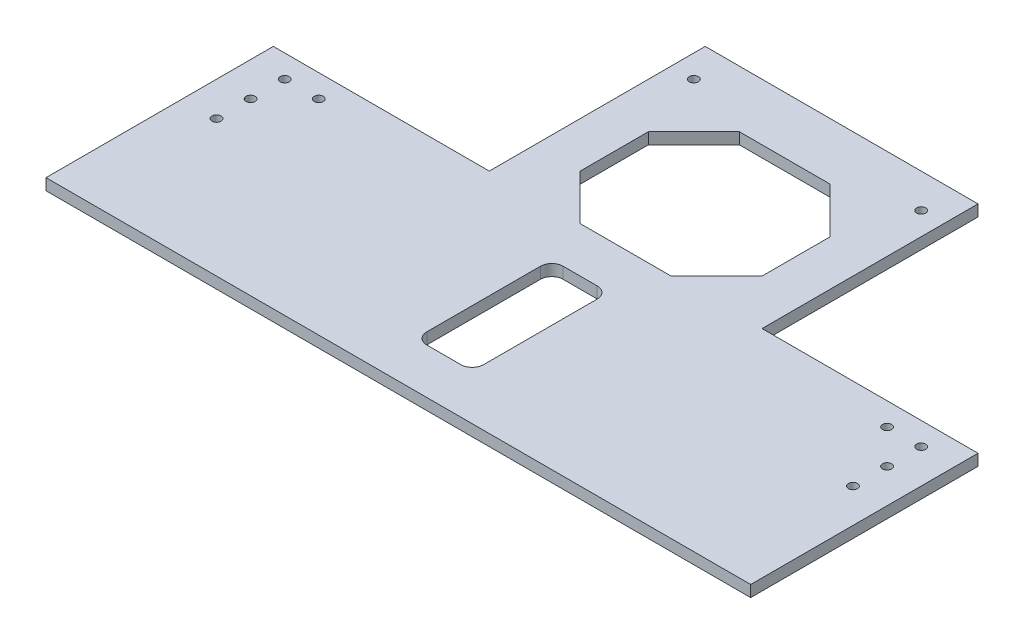
SolidWorks part; units mm, degrees
ref_plane "前视基准面" through (0, 0, 0) normal (0, 0, 1) x (1, 0, 0)
ref_plane "上视基准面" through (0, 0, 0) normal (0, 1, 0) x (1, 0, 0)
ref_plane "右视基准面" through (0, 0, 0) normal (1, 0, 0) x (0, 0, -1)
sketch "Sketch1" plane through (0, 0, 0) normal (0, 1, 0) x (1, 0, 0)
  line L0 (0, 50) -> (0, 97.5) construction
  line L1 (-155, 50) -> (155, 50)
  line L2 (-155, 50) -> (-155, -50)
  line L3 (-155, -50) -> (155, -50)
  line L4 (155, 50) -> (155, -50)
  line L5 (-155, 50) -> (155, -50) construction
  line L6 (-155, -50) -> (155, 50) construction
  line L8 (-60, 145) -> (60, 145)
  line L9 (-60, 145) -> (-60, 50)
  line L10 (-60, 50) -> (60, 50)
  line L11 (60, 145) -> (60, 50)
  line L12 (-60, 145) -> (60, 50) construction
  line L13 (-60, 50) -> (60, 145) construction
  point P0 (0, 0)
  dimension "D1" = 310
  dimension "100" = 100
  dimension "D2" = 120
  dimension "D3" = 95
extrude "Boss-Extrude1" add sketch "Sketch1" along normal blind 5 contours L11 L8 L9 L1 | L4 L1 L2 L3 region at (0, 0, 0) region at (0, 0, -97.5)
sketch "Sketch2" plane through (0, 5, 0) normal (0, 1, 0) x (1, 0, 0)
  line L0 (-140, -50) -> (-140, 50) construction
  line L1 (-155, -50) -> (155, -50) construction
  line L2 (-155, 50) -> (-60, 50) construction
  line L3 (0, 0) -> (0, 145) construction
  line L4 (-60, 145) -> (60, 145) construction
  line L5 (-155, 50) -> (-155, -50) construction
  line L6 (-155, 40) -> (155, 40) construction
  line L7 (-12.5, -30) -> (12.5, -30)
  line L8 (-12.5, -30) -> (-12.5, 30)
  line L9 (-12.5, 30) -> (12.5, 30)
  line L10 (12.5, -30) -> (12.5, 30)
  line L11 (-12.5, -30) -> (12.5, 30) construction
  line L12 (-12.5, 30) -> (12.5, -30) construction
  line L13 (-50, 145) -> (-50, 40) construction
  line L14 (-60, 145) -> (-60, 50) construction
  line L15 (140, -50) -> (140, 50) construction
  line L16 (50, 145) -> (50, 40) construction
  circle A0 centre (-140, 40) radius 2
  circle A2 centre (-125, 40) radius 2
  circle A3 centre (-140, 25) radius 2
  circle A4 centre (-140, 10) radius 2
  circle A5 centre (140, 10) radius 2
  circle A6 centre (140, 25) radius 2
  circle A7 centre (125, 40) radius 2
  circle A8 centre (140, 40) radius 2
  circle A9 centre (-50, 130) radius 2
  circle A10 centre (50, 130) radius 2
  point P26 (0, 40)
  dimension "D6" = 4
  dimension "D7" = 15
  dimension "D8" = 15
  dimension "D9" = 15
  dimension "D10" = 15
  dimension "D11" = 4
  dimension "D1" = 15
  dimension "D2" = 25
  dimension "D3" = 20
  dimension "D4" = 10
  dimension "D5" = 10
extrude "Cut-Extrude1" cut sketch "Sketch2" against normal through all
fillet "Fillet1" radius 5 4 edges at (-12.5, 2.5, 30) (12.5, 2.5, -30) (12.5, 2.5, 30) (-12.5, 2.5, -30)
sketch "Sketch5" plane through (0, 5, 0) normal (0, 1, 0) x (1, 0, 0)
  line L0 (-60, 50) -> (60, 50) construction
  line L1 (0, 50) -> (0, 85) construction
  line L3 (-40, 120) -> (40, 120)
  line L4 (-40, 120) -> (-40, 50)
  line L5 (-40, 50) -> (40, 50)
  line L6 (40, 120) -> (40, 50)
  line L7 (-40, 120) -> (40, 50) construction
  line L8 (-40, 50) -> (40, 120) construction
  line L9 (-60, 145) -> (60, 145) construction
  dimension "D1" = 70
  dimension "D2" = 80
  dimension "D3" = 25
extrude "Cut-Extrude2" cut sketch "Sketch5" against normal blind 5 contours L4 L3 L6 L5
chamfer "Chamfer1" distance 20 angle 45 4 edges at (-40, 2.5, -50) (40, 2.5, -50) (40, 2.5, -120) (-40, 2.5, -120)
